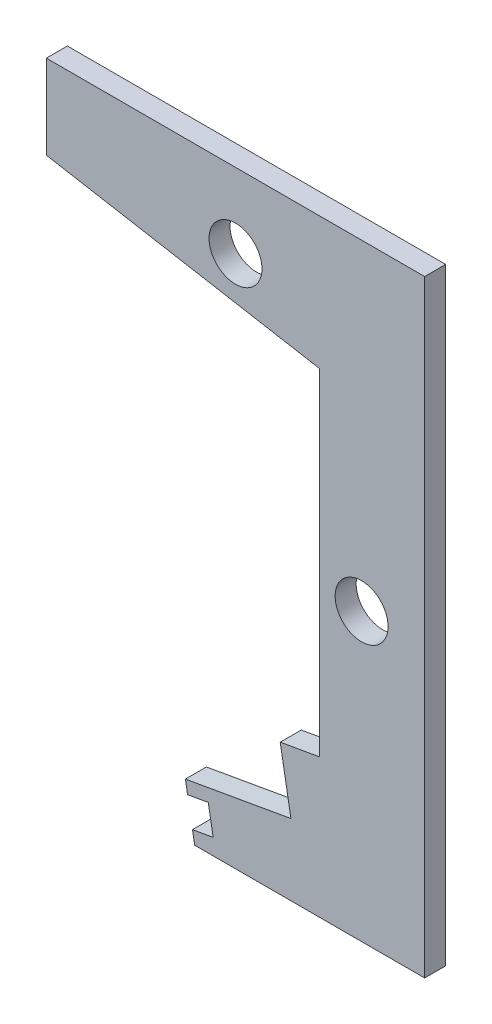
SolidWorks part; units mm, degrees
material "Balsa"
ref_plane "Plan de face" through (0, 0, 0) normal (0, 0, 1) x (1, 0, 0)
ref_plane "Plan de dessus" through (0, 0, 0) normal (0, 1, 0) x (1, 0, 0)
ref_plane "Plan de droite" through (0, 0, 0) normal (1, 0, 0) x (0, 0, -1)
sketch "Esquisse1" plane through (0, 0, 0) normal (0, 0, 1) x (1, 0, 0)
  line L0 (-65, 51.4613) -> (0, 40)
  line L1 (0, 40) -> (0, -40)
  line L2 (-6.8091, -56.1122) -> (-9.3591, -41.6503)
  line L3 (-9.3591, -41.6503) -> (0, -40)
  line L4 (-6.8091, -56.1122) -> (-31.9182, -60.5396)
  line L5 (-29.71, -73.063) -> (25, -73.063)
  line L6 (25, -73.063) -> (25, 71.4613)
  line L7 (25, 71.4613) -> (-65, 71.4613)
  line L8 (-65, 71.4613) -> (-65, 51.4613)
  line L9 (7.1417, -5.2313) -> (92.0944, -5.2313) construction
  line L10 (-31.9182, -60.5396) -> (-29.71, -73.063)
  circle A0 centre (-20, 53.6808) radius 6.3
  circle A1 centre (10, -5) radius 6.3
  dimension "D1" = 12.6
  dimension "D15" = 12.6
  dimension "D2" = 10
  dimension "D3" = 20
  dimension "D4" = 80
  dimension "D5" = 65
  dimension "D6" = 100
  dimension "D7" = 100
  dimension "D8" = 20
  dimension "D9" = 35
  dimension "D10" = 90
  dimension "D11" = 9.5035
  dimension "D12" = 14.685
  dimension "D13" = 10
  dimension "D14" = 35
extrude "Boss.-Extru.1" add sketch "Esquisse1" along normal blind 5
sketch "Esquisse2" plane through (0, 0, 0) normal (0, 0, -1) x (-1, 0, 0)
  line L0 (31.3966, -63.498) -> (30.231, -70.1086)
  line L1 (31.3966, -63.498) -> (26.4726, -62.6297)
  line L2 (30.231, -70.1086) -> (25.3069, -69.2404)
  line L3 (26.4726, -62.6297) -> (25.3069, -69.2404)
  line L11 (31.9182, -60.5396) -> (29.71, -73.063) construction
  line L12 (6.8091, -56.1122) -> (31.9182, -60.5396) construction
  dimension "D2" = 5
  dimension "D3" = 3.004
  dimension "D4" = 3
extrude "Enlèv. mat.-Extru.1" cut sketch "Esquisse2" against normal blind 5
